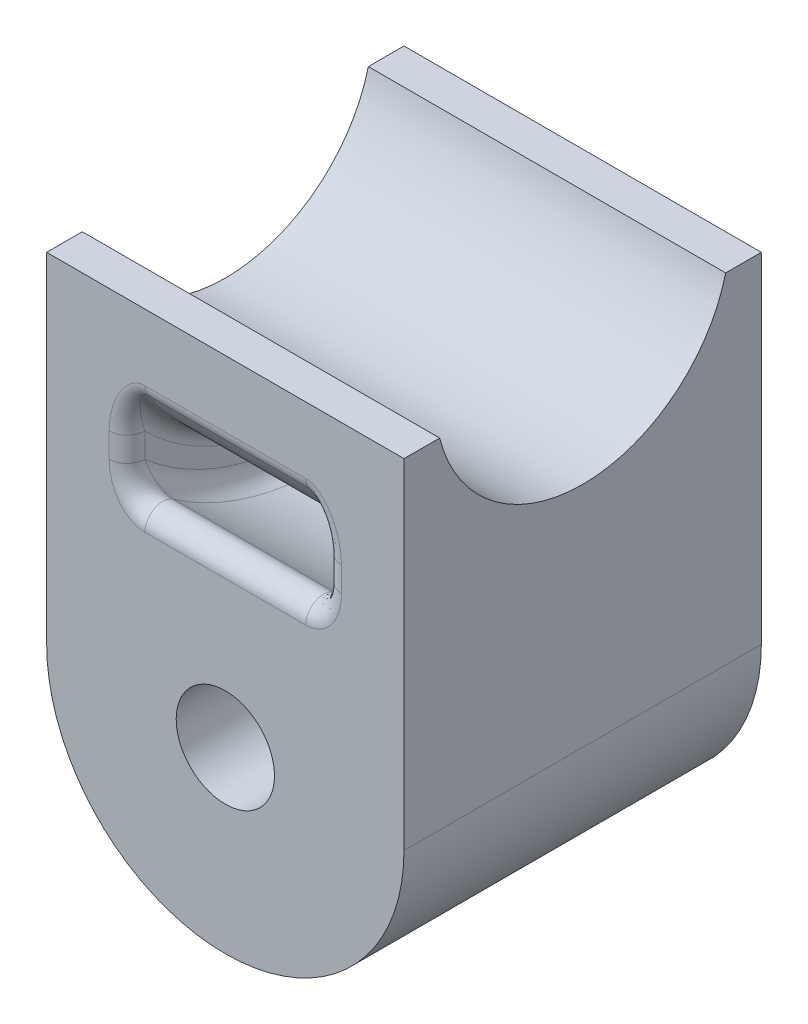
SolidWorks part; units mm, degrees
ref_plane "Спереди" through (0, 0, 0) normal (0, 0, 1) x (1, 0, 0)
ref_plane "Сверху" through (0, 0, 0) normal (0, 1, 0) x (1, 0, 0)
ref_plane "Справа" through (0, 0, 0) normal (1, 0, 0) x (0, 0, -1)
sketch "Эскиз1" plane through (0, 0, 0) normal (0, 1, 0) x (1, 0, 0)
  line L1 (-10, 10) -> (10, 10)
  line L2 (-10, 10) -> (-10, -10)
  line L3 (-10, -10) -> (10, -10)
  line L4 (10, 10) -> (10, -10)
  line L5 (-10, 10) -> (10, -10) construction
  line L6 (-10, -10) -> (10, 10) construction
  point P0 (0, 0)
  dimension "D1" = 20
  dimension "D2" = 20
extrude "Бобышка-Вытянуть1" add sketch "Эскиз1" along normal blind 14
sketch "Эскиз2" plane through (-10, 0, 0) normal (-1, 0, 0) x (0, 0, 1)
  line L0 (-10, 14) -> (10, 14) construction
  circle A0 centre (0, 16) radius 8.25
  dimension "D1" = 16.5
  dimension "D2" = 2
extrude "Вырез-Вытянуть1" cut sketch "Эскиз2" against normal through all
sketch "Эскиз3" plane through (0, 0, 0) normal (1, 0, 0) x (0, 0, -1)
  line L0 (-10, 14) -> (-10, 10) construction
  line L1 (-10, 14) -> (-10, 0) construction
  circle A0 centre (0, 16) radius 11.6619
  circle A1 centre (0, 16) radius 14.6619
  arc A2 (-8.0039, 14) -> (8.0039, 14) centre (0, 16) ccw construction
  dimension "D1" = 4
  dimension "D2" = 3
extrude "Вырез-Вытянуть2" cut sketch "Эскиз3" against normal mid plane 11
fillet "Скругление1" radius 1 12 edges at (0, 5.2775, -10) (5.5, 1.3381, 0) (0, 5.2775, 10) (-5.5, 1.3381, 0) (-5.5, 4.3381, 0) (0, 10, 10) (5.5, 4.3381, 0) (0, 10, -10) (-5.5, 7.6388, 10) (-5.5, 7.6388, -10) (5.5, 7.6388, 10) (5.5, 7.6388, -10)
sketch "Эскиз4" plane through (0, 0, -10) normal (0, 0, -1) x (-1, 0, 0)
  line L1 (-10, 0) -> (-10, -5)
  line L2 (-10, 0) -> (10, 0)
  line L3 (10, 0) -> (10, -5)
  circle A0 centre (0, -5) radius 2.75 construction
  arc A1 (-10, -5) -> (10, -5) centre (0, -5) ccw
  line M8 (-10, 0) -> (10, 0)
  dimension "D1" = 5.5
  dimension "D2" = 5
extrude "Бобышка-Вытянуть2" add sketch "Эскиз4" against normal up to surface (20 mm away) contours L1 A1 L3 M8 region at (0, -6.6208, -10) up to face at (-0.0005, 6.6459, 10)
sketch "Эскиз5" plane through (0, 0, -10) normal (0, 0, -1) x (-1, 0, 0)
  circle A0 centre (0, -5) radius 2.75
  arc A1 (-10, -5) -> (10, -5) centre (0, -5) ccw construction
  dimension "D1" = 5.5
extrude "Вырез-Вытянуть3" cut sketch "Эскиз5" against normal through all
equation "\"print_offset\"= 0.5"
equation "\"screw_m5_d\"= 5"
equation "\"screw_m5_hh_d\"= 9.5"
equation "\"nut_m5_d\"= 7.9"
equation "\"nut_m5_h\"= 3.9"
equation "\"tube_d\"= 16"
equation "\"tube_tape_d\"= 3"
equation "\"tube_tape_h\"= 11"
equation "\"D2@Эскиз1\"=\"D1@Эскиз1\""
equation "\"D1@Эскиз2\"=\"tube_d\"+\"print_offset\""
equation "\"D2@Эскиз3\"=\"tube_tape_d\""
equation "\"D1@Вырез-Вытянуть2\"=\"tube_tape_h\""
equation "\"D1@Эскиз4\"=\"screw_m5_d\"+\"print_offset\""
equation "\"D1@Эскиз5\"=\"screw_m5_d\"+\"print_offset\""
